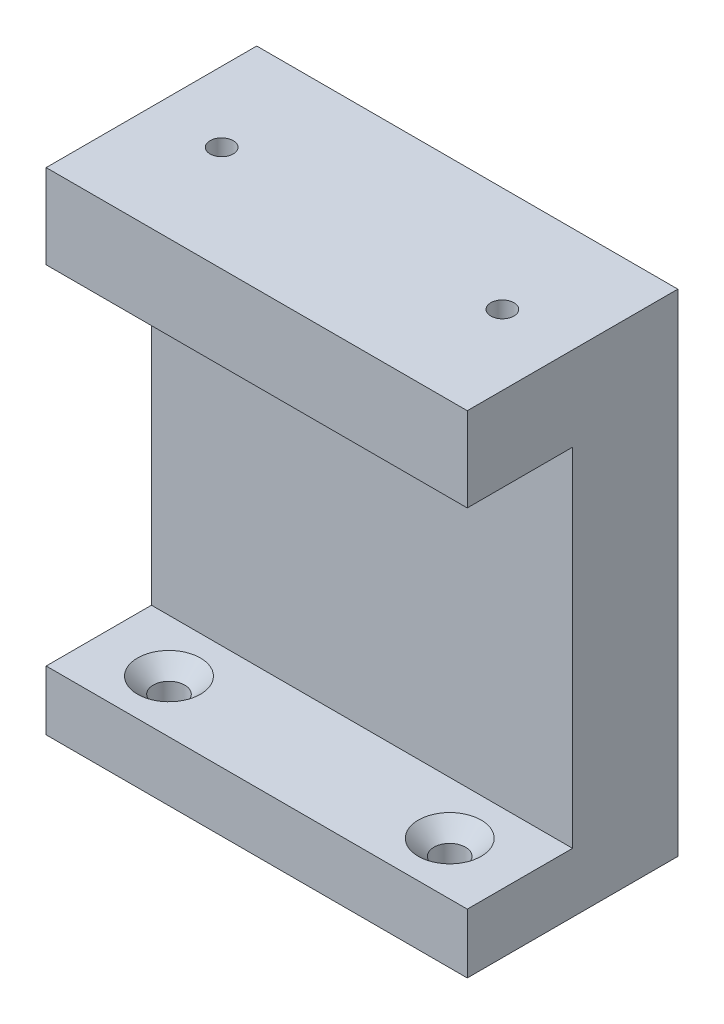
SolidWorks part; units mm, degrees
ref_plane "Front Plane" through (0, 0, 0) normal (0, 0, 1) x (1, 0, 0)
ref_plane "Top Plane" through (0, 0, 0) normal (0, 1, 0) x (1, 0, 0)
ref_plane "Right Plane" through (0, 0, 0) normal (1, 0, 0) x (0, 0, -1)
sketch "Sketch1" plane through (0, 0, 0) normal (0, 1, 0) x (1, 0, 0)
  line L1 (-30, -15) -> (30, -15)
  line L2 (-30, -15) -> (-30, 15)
  line L3 (-30, 15) -> (30, 15)
  line L4 (30, -15) -> (30, 15)
  line L5 (-30, -15) -> (30, 15) construction
  line L6 (-30, 15) -> (30, -15) construction
  point P0 (0, 0)
  dimension "D1" = 60
  dimension "D2" = 30
extrude "Boss-Extrude1" add sketch "Sketch1" along normal blind 70
sketch "Sketch2" plane through (30, 0, 0) normal (1, 0, 0) x (0, 0, -1)
  line L0 (-15, 70) -> (15, 70) construction
  line L1 (-15, 8.5) -> (0, 8.5)
  line L2 (-15, 8.5) -> (-15, 58)
  line L3 (-15, 58) -> (0, 58)
  line L4 (0, 8.5) -> (0, 58)
  line L5 (-15, 8.5) -> (0, 58) construction
  line L6 (-15, 58) -> (0, 8.5) construction
  line L7 (-15, 0) -> (15, 0) construction
  line L8 (-15, 70) -> (-15, 0) construction
  point P0 (-7.5, 33.25)
  point P9 (0, 0)
  dimension "D1" = 15
  dimension "D2" = 12
  dimension "D3" = 8.5
extrude "Cut-Extrude1" cut sketch "Sketch2" against normal blind 90
hole_wizard "CSK for M4 SFHCS1" positions "Sketch3" profile "Sketch4" countersink size "M4" standard "ANSI Metric" end condition through all
sketch "Sketch3" plane through (0, 8.5, 0) normal (0, 1, 0) x (1, 0, 0)
  line L0 (-20, -7.5) -> (20, -7.5)
  point P1 (-20, -7.5)
  point P2 (20, -7.5)
  point P5 (0, -7.5)
  dimension "D1" = 40
  dimension "D2" = 7.5
sketch "Sketch4" plane through (-20, 8.5, 7.5) normal (1, 0, 0) x (0, 0, 1)
  line L0 (0, 0) -> (0, 8.5)
  line L1 (0, 8.5) -> (2.25, 8.5)
  line L2 (2.25, 8.5) -> (2.25, 2.23)
  line L3 (2.25, 2.23) -> (4.48, 0)
  line L5 (4.48, 0) -> (0, 0)
  line L6 (-2.25, 2.23) -> (-4.48, 0) construction
  line L11 (0, -6.35) -> (0, 107.95) construction
  dimension "Thru Hole Dia." = 4.5
  dimension "Thru Hole Depth" = 8.5
  dimension "Near C'Sink Dia." = 8.96
  dimension "Near C'Sink Angle" = 90
hole_wizard "M4x0.7 Tapped Hole1" positions "Sketch5" profile "Sketch7" tap size "M4x0.7" standard "ANSI Metric"
sketch "Sketch5" plane through (0, 0, -15) normal (0, 0, -1) x (-1, 0, 0)
  line L1 (-20, 15) -> (20, 15)
  line L2 (-20, 15) -> (-20, 55)
  line L3 (-20, 55) -> (20, 55)
  line L4 (20, 15) -> (20, 55)
  line L5 (-20, 15) -> (20, 55) construction
  line L6 (-20, 55) -> (20, 15) construction
  line L7 (-30, 0) -> (30, 0) construction
  point P1 (20, 55)
  point P52 (-20, 15)
  point P53 (-20, 55)
  point P54 (20, 15)
  point P66 (0, 35)
  dimension "D1" = 40
  dimension "D2" = 40
  dimension "D3" = 35
sketch "Sketch7" plane through (-20, 55, -15) normal (1, 0, 0) x (0, 1, 0)
  line L0 (0, 0) -> (0, 10.9914)
  line L1 (0, 10.9914) -> (1.65, 10)
  line L2 (1.65, 10) -> (1.65, 0)
  line L5 (1.65, 0) -> (0, 0)
  line L10 (0, 10.9914) -> (-1.65, 10) construction
  line L11 (0, -6.35) -> (0, 107.95) construction
  dimension "Tap Drill Dia." = 3.3
  dimension "Tap Drill Depth" = 10
  dimension "Drill Angle" = 118
cosmetic thread "Hole Thread1" parameters "D1"=8, "D2"=4
cosmetic thread "Hole Thread2" parameters "D1"=8, "D2"=4
cosmetic thread "Hole Thread3" parameters "D1"=8, "D2"=4
cosmetic thread "Hole Thread4" parameters "D1"=8, "D2"=4
hole_wizard "M4x0.7 Tapped Hole2" positions "Sketch8" profile "Sketch10" tap size "M4x0.7" standard "ANSI Metric"
sketch "Sketch8" plane through (0, 70, 0) normal (0, 1, 0) x (1, 0, 0)
  line L0 (-20, 0) -> (20, 0)
  point P0 (-20, 0)
  point P1 (20, 0)
  point P3 (0, 0)
  dimension "D1" = 40
sketch "Sketch10" plane through (-20, 70, 0) normal (1, 0, 0) x (0, 0, 1)
  line L0 (0, 0) -> (0, 12.9914)
  line L1 (0, 12.9914) -> (1.65, 12)
  line L2 (1.65, 12) -> (1.65, 0)
  line L5 (1.65, 0) -> (0, 0)
  line L10 (0, 12.9914) -> (-1.65, 12) construction
  line L11 (0, -6.35) -> (0, 107.95) construction
  dimension "Tap Drill Dia." = 3.3
  dimension "Tap Drill Depth" = 12
  dimension "Drill Angle" = 118
cosmetic thread "Hole Thread5" parameters "D1"=8, "D2"=4
cosmetic thread "Hole Thread6" parameters "D1"=8, "D2"=4
